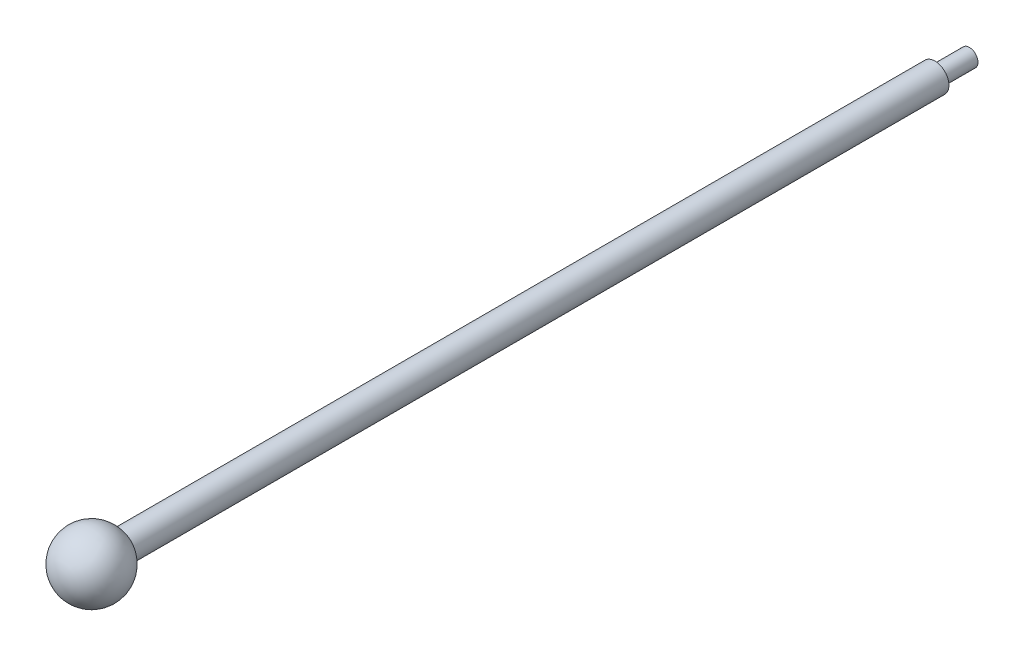
SolidWorks part; units mm, degrees
ref_plane "Płaszczyzna przednia" through (0, 0, 0) normal (0, 0, 1) x (1, 0, 0)
ref_plane "Płaszczyzna górna" through (0, 0, 0) normal (0, 1, 0) x (1, 0, 0)
ref_plane "Płaszczyzna prawa" through (0, 0, 0) normal (1, 0, 0) x (0, 0, -1)
sketch "Szkic1" plane through (0, 0, 0) normal (0, 0, 1) x (1, 0, 0)
  line L0 (0, 15) -> (0, -15)
  arc A2 (0, -15) -> (0, 15) centre (0, 0) cw
  dimension "D1" = 15
revolve "Obrót5" add sketch "Szkic1" angle 360 about L0
ref_plane "Płaszczyzna1" through (0, 0, -15) normal (0, 0, -1) x (-1, 0, 0)
sketch "Szkic2" plane through (0, 0, -15) normal (0, 0, -1) x (-1, 0, 0)
  circle A0 centre (0, 0) radius 6.5
  dimension "D1" = 13
extrude "Dodanie-wyciągnięcie1" add sketch "Szkic2" along normal blind 376.5 and the other way up to next contours A0
sketch "Szkic3" plane through (0, 0, -391.5) normal (0, 0, -1) x (-1, 0, 0)
  circle A0 centre (0, 0) radius 4
  dimension "D1" = 8
extrude "Dodanie-wyciągnięcie2" add sketch "Szkic3" along normal blind 16 contours A0
ref_plane "Płaszczyzna2" through (0, 6.5, 0) normal (0, 1, 0) x (1, 0, 0)
ref_axis "Oś1" through (0, 0, -13.5185) along (0, 0, -1)
